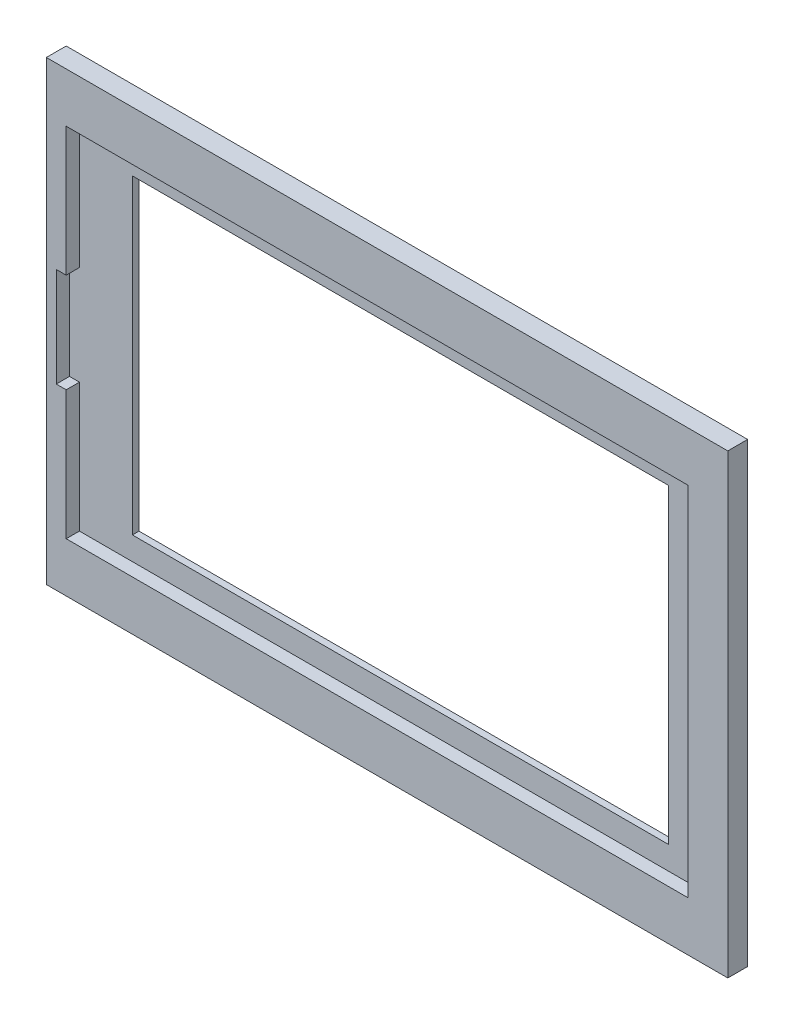
SolidWorks part; units mm, degrees
ref_plane "Front Plane" through (0, 0, 0) normal (0, 0, 1) x (1, 0, 0)
ref_plane "Top Plane" through (0, 0, 0) normal (0, 1, 0) x (1, 0, 0)
ref_plane "Right Plane" through (0, 0, 0) normal (1, 0, 0) x (0, 0, -1)
sketch "Sketch1" plane through (0, 0, 0) normal (0, 0, 1) x (1, 0, 0)
  line L1 (113.8284, 62.9439) -> (10.8284, 62.9439)
  line L2 (113.8284, 62.9439) -> (113.8284, -6.0561)
  line L3 (113.8284, -6.0561) -> (10.8284, -6.0561)
  line L4 (10.8284, 62.9439) -> (10.8284, -6.0561)
  dimension "D1" = 69
  dimension "D2" = 103
extrude "Boss-Extrude1" add sketch "Sketch1" along normal blind 3
sketch "Sketch2" plane through (0, 0, 3) normal (0, 0, 1) x (1, 0, 0)
  line L0 (10.8284, 62.9439) -> (10.8284, -6.0561) construction
  line L1 (21.8284, 51.9439) -> (102.8284, 51.9439)
  line L2 (21.8284, 51.9439) -> (21.8284, 4.9439)
  line L3 (21.8284, 4.9439) -> (102.8284, 4.9439)
  line L4 (102.8284, 51.9439) -> (102.8284, 4.9439)
  line L5 (113.8284, 62.9439) -> (10.8284, 62.9439) construction
  line L6 (113.8284, -6.0561) -> (113.8284, 62.9439) construction
  line L7 (10.8284, -6.0561) -> (113.8284, -6.0561) construction
  dimension "D1" = 11
  dimension "D2" = 11
  dimension "D3" = 11
  dimension "D4" = 11
extrude "Cut-Extrude1" cut sketch "Sketch2" against normal blind 3
sketch "Sketch3" plane through (0, 0, 3) normal (0, 0, 1) x (1, 0, 0)
  line L0 (113.8284, -6.0561) -> (113.8284, 62.9439) construction
  line L1 (13.8284, 55.4439) -> (107.8284, 55.4439)
  line L2 (13.8284, 55.4439) -> (13.8284, 35.9439)
  line L3 (13.8284, 1.4439) -> (107.8284, 1.4439)
  line L5 (10.8284, 62.9439) -> (10.8284, -6.0561) construction
  line L11 (107.8284, 55.4439) -> (107.8284, 1.4439)
  line L12 (13.8284, 20.9439) -> (13.8284, 1.4439)
  line L13 (13.8284, 35.9439) -> (12.3284, 35.9439)
  line L15 (13.8284, 20.9439) -> (12.3284, 20.9439)
  line L16 (12.3284, 35.9439) -> (12.3284, 20.9439)
  point P13 (113.8284, 28.4439)
  point P14 (107.8284, 28.4439)
  dimension "D1" = 94
  dimension "D2" = 54
  dimension "D3" = 3
  dimension "D4" = 1.5
  dimension "D5" = 15
  dimension "D6" = 19.5
extrude "Cut-Extrude2" cut sketch "Sketch3" against normal blind 2
